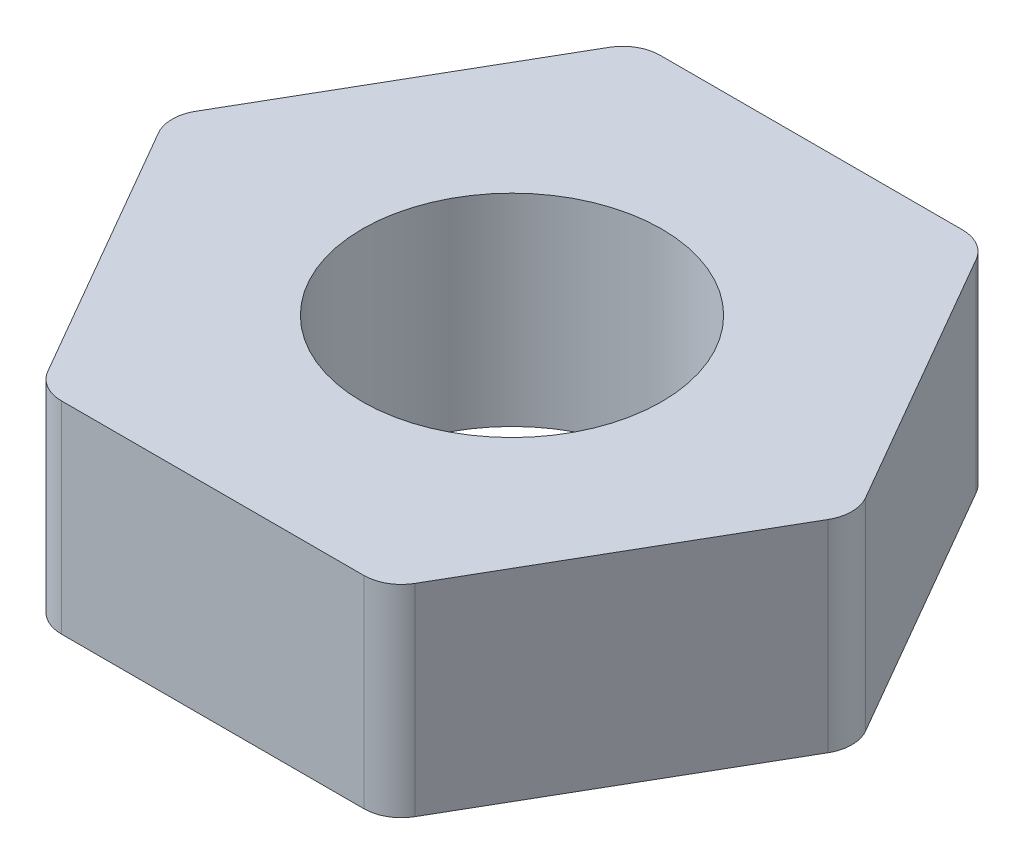
SolidWorks part; units mm, degrees
material "1.4000 (X6Cr13)"
ref_plane "Спереди" through (0, 0, 0) normal (0, 0, 1) x (1, 0, 0)
ref_plane "Сверху" through (0, 0, 0) normal (0, 1, 0) x (1, 0, 0)
ref_plane "Справа" through (0, 0, 0) normal (1, 0, 0) x (0, 0, -1)
sketch "Эскиз1" plane through (0, 0, 0) normal (0, 1, 0) x (1, 0, 0)
  line L1 (4.6188, 0) -> (2.3094, 4)
  line L2 (2.3094, 4) -> (-2.3094, 4)
  line L3 (-2.3094, 4) -> (-4.6188, 0)
  line L4 (-4.6188, 0) -> (-2.3094, -4)
  line L5 (-2.3094, -4) -> (2.3094, -4)
  line L6 (2.3094, -4) -> (4.6188, 0)
  circle A0 centre (0, 0) radius 4 construction
  circle A1 centre (0, 0) radius 2
  dimension "D1" = 8
  dimension "D2" = 4
extrude "Бобышка-Вытянуть1" add sketch "Эскиз1" along normal blind 2.7
sketch "Эскиз2" plane through (0, 0, 0) normal (0, 0, 1) x (1, 0, 0)
  line L0 (0, 0) -> (0, 2.7) construction
  line L1 (4.5, 4.1362) -> (3.3117, 3.4502)
  line L2 (3.3117, 3.4502) -> (3.3117, 4.1362)
  line L3 (3.3117, 4.1362) -> (4.5, 4.1362)
  line L4 (6.3509, 4.1362) -> (7.814, 3.2915)
  line L5 (7.814, 3.2915) -> (7.814, 4.1362)
  line L6 (7.814, 4.1362) -> (6.3509, 4.1362)
  line L7 (2, 2.7) -> (-2, 2.7) construction
  line L8 (0, 1.35) -> (8.41, 1.35) construction
  line L9 (7.814, -1.4362) -> (6.3509, -1.4362)
  line L10 (7.814, -0.5915) -> (7.814, -1.4362)
  line L11 (6.3509, -1.4362) -> (7.814, -0.5915)
  line L12 (3.3117, -1.4362) -> (4.5, -1.4362)
  line L13 (3.3117, -0.7502) -> (3.3117, -1.4362)
  line L14 (4.5, -1.4362) -> (3.3117, -0.7502)
  dimension "D1" = 4.5
  dimension "D2" = 30
  dimension "D3" = 30
revolve "Вырез-Повернуть1" [suppressed] cut sketch "Эскиз2" angle 360 about L0 other way angle 360
fillet "Скругление1" radius 0.5 6 edges at (-4.6188, 1.35, 0) (-2.3094, 1.35, 4) (2.3094, 1.35, 4) (4.6188, 1.35, 0) (-2.3094, 1.35, -4) (2.3094, 1.35, -4)
sketch "Эскиз3" plane through (0, 2.7, 0) normal (0, 1, 0) x (1, 0, 0)
  circle A0 centre (0, 0) radius 4
  dimension "D1" = 8
curve "Спираль1" [suppressed] pitch 1.2 height 4.2 turns 3.5
sketch "Эскиз5" [suppressed] plane through (0, 0, 0) normal (1, 0, 0) x (0, 0, -1)
  line L0 (-4, 4) -> (-3, 4) construction
  line L1 (-3, 4) -> (-3, 3.4226) construction
  line L2 (-3, 3.4226) -> (-4, 4) construction
  line L3 (-4, 4) -> (-3, 4.5774) construction
  line L4 (-3, 4.5774) -> (-3, 4) construction
  line L5 (-4, 4) -> (-3, 3.4226)
  line L6 (-3, 3.4226) -> (-3, 4.5774)
  line L7 (-3, 4.5774) -> (-4, 4)
  dimension "D1" = 30
  dimension "D2" = 30
  dimension "D3" = 1
sweep "Вырез-По траектории1" [suppressed] cut profiles "Эскиз5" path "Спираль1"
